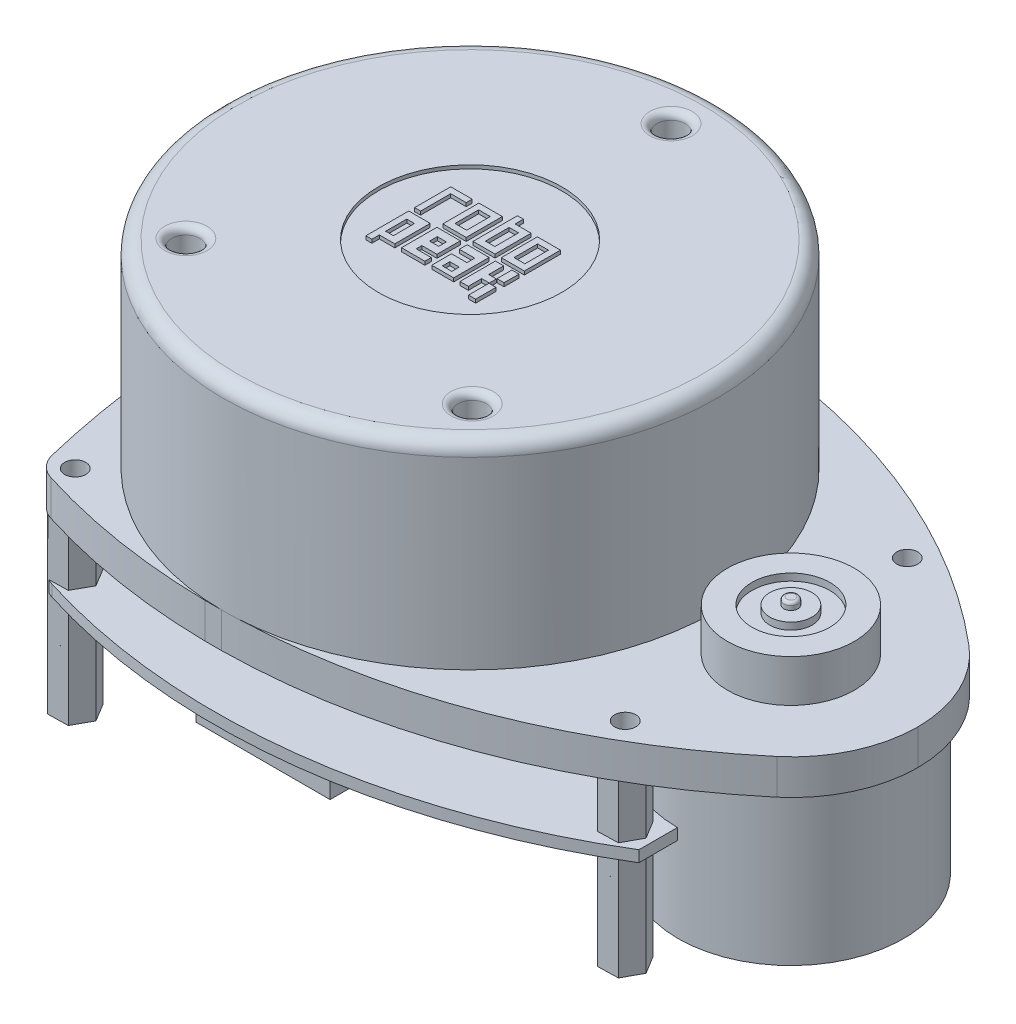
SolidWorks part; units mm, degrees
ref_plane "Спереди" through (0, 0, 0) normal (0, 0, 1) x (1, 0, 0)
ref_plane "Сверху" through (0, 0, 0) normal (0, 1, 0) x (1, 0, 0)
ref_plane "Справа" through (0, 0, 0) normal (1, 0, 0) x (0, 0, -1)
sketch "Эскиз1" plane through (0, 0, 0) normal (0, 1, 0) x (1, 0, 0)
  line L1 (-49.25, 35) -> (49.25, 35)
  line L2 (-49.25, 35) -> (-49.25, -35)
  line L3 (-49.25, -35) -> (49.25, -35)
  line L4 (49.25, 35) -> (49.25, -35)
  line L5 (-49.25, 35) -> (49.25, -35) construction
  line L6 (-49.25, -35) -> (49.25, 35) construction
  point P0 (0, 0)
  dimension "D1" = 98.5
  dimension "D2" = 70
extrude "Бобышка-Вытянуть1" add sketch "Эскиз1" along normal blind 5
sketch "Эскиз2" plane through (0, 5, 0) normal (0, 1, 0) x (1, 0, 0)
  line L0 (-49.25, 35) -> (-49.25, -35) construction
  circle A0 centre (-14.25, 0) radius 35
  point P2 (-49.25, 0)
  point P3 (-49.25, 0)
extrude "Бобышка-Вытянуть2" add sketch "Эскиз2" along normal blind 28.1
sketch "Эскиз3" plane through (0, 33.1, 0) normal (0, 1, 0) x (1, 0, 0)
  line L0 (-14.25, 0) -> (-14.25, 50000) construction
  line L1 (-14.25, -20) -> (-26.2883, -20) construction
  line L2 (-49.25, -35) -> (-14.25, -35) construction
  circle A0 centre (-14.25, 28.5) radius 2
  circle A1 centre (-34.5539, -20) radius 2
  circle A2 centre (6.0539, -20) radius 2
  arc A3 (-49.25, 0) -> (-14.25, -35) centre (-14.25, 0) ccw construction
  circle A4 centre (-14.25, 0) radius 35 construction
  dimension "D2" = 4
  dimension "D1" = 6.5
  dimension "D3" = 15
  dimension "D4" = 28.5
  dimension "D5" = 28.5
extrude "Вырез-Вытянуть1" cut sketch "Эскиз3" against normal blind 5
fillet "Скругление1" radius 2 1 edges at (-14.25, 33.1, 35)
fillet "Скругление2" radius 1 3 edges at (6.0539, 33.1, 22) (-34.5539, 33.1, 22) (-14.25, 33.1, -26.5)
sketch "Эскиз4" plane through (0, 33.1, 0) normal (0, 1, 0) x (1, 0, 0)
  line L0 (-22.1152, -6.9149) -> (-22.1152, -0.8316)
  line L1 (-22.1152, -0.8316) -> (-19.0735, -0.8316)
  line L2 (-19.0735, -0.8316) -> (-19.0735, -5.8538)
  line L3 (-19.0735, -5.8538) -> (-21.2663, -5.8538)
  line L4 (-21.2663, -5.8538) -> (-21.2663, -6.9149)
  line L5 (-21.2663, -6.9149) -> (-22.1152, -6.9149)
  line L6 (-22.1152, 0) -> (-22.1152, 5.1201)
  line L7 (-22.1152, 5.1201) -> (-19.0735, 5.1201)
  line L8 (-19.0735, 5.1201) -> (-19.0735, 4.2707)
  line L9 (-19.0735, 4.2707) -> (-21.2663, 4.2707)
  line L10 (-21.2663, 4.2707) -> (-21.2663, 0)
  line L11 (-21.2663, 0) -> (-22.1152, 0)
  line L12 (-21.2663, -1.9579) -> (-20.1699, -1.9579)
  line L13 (-20.1699, -1.9579) -> (-20.1699, -4.9509)
  line L14 (-20.1699, -4.9509) -> (-21.2663, -4.9509)
  line L15 (-21.2663, -4.9509) -> (-21.2663, -1.9579)
  line L16 (-13.8296, 0) -> (-13.8296, 6.293)
  line L17 (-18.1168, 0) -> (-14.8003, 0)
  line L18 (-18.1168, 0) -> (-18.1168, 5.1201)
  line L19 (-18.1168, 5.1201) -> (-14.8003, 5.1201)
  line L20 (-14.8003, 0) -> (-14.8003, 5.1201)
  line L21 (-9.8255, 5.1201) -> (-6.5494, 5.1201)
  line L22 (-9.8255, 5.1201) -> (-9.8255, 0)
  line L23 (-9.8255, 0) -> (-6.5494, 0)
  line L24 (-6.5494, 5.1201) -> (-6.5494, 0)
  line L25 (-8.9357, 4.2707) -> (-7.3988, 4.2707)
  line L26 (-8.9357, 4.2707) -> (-8.9357, 0.9137)
  line L27 (-8.9357, 0.9137) -> (-7.3988, 0.9137)
  line L28 (-7.3988, 4.2707) -> (-7.3988, 0.9137)
  line L29 (-17.3079, 4.2707) -> (-15.6497, 4.2707)
  line L30 (-17.3079, 4.2707) -> (-17.3079, 0.9137)
  line L31 (-17.3079, 0.9137) -> (-15.6497, 0.9137)
  line L32 (-15.6497, 4.2707) -> (-15.6497, 0.9137)
  line L33 (-12.9802, 4.2707) -> (-11.6455, 4.2707)
  line L34 (-12.9802, 4.2707) -> (-12.9802, 0.9137)
  line L35 (-12.9802, 0.9137) -> (-11.6455, 0.9137)
  line L36 (-11.6455, 4.2707) -> (-11.6455, 0.9137)
  line L37 (-12.9802, -4.142) -> (-11.6455, -4.142)
  line L38 (-12.9802, -4.142) -> (-12.9802, -5.1936)
  line L39 (-12.9802, -5.1936) -> (-11.6455, -5.1936)
  line L40 (-11.6455, -4.142) -> (-11.6455, -5.1936)
  line L41 (-16.9439, -1.9579) -> (-15.6497, -1.9579)
  line L42 (-16.9439, -1.9579) -> (-16.9439, -3.0499)
  line L43 (-16.9439, -3.0499) -> (-15.6497, -3.0499)
  line L44 (-15.6497, -1.9579) -> (-15.6497, -3.0499)
  line L46 (-7.5508, -0.7643) -> (-6.5494, -0.7643)
  line L47 (-7.5508, -0.7643) -> (-7.5508, -2.8858)
  line L48 (-7.5508, -2.8858) -> (-6.5494, -2.8858)
  line L49 (-6.5494, -0.7643) -> (-6.5494, -2.8858)
  line L50 (-6.5494, -6.9149) -> (-7.5508, -6.9149)
  line L51 (-6.5494, -6.9149) -> (-6.5494, -4.0216)
  line L52 (-6.5494, -4.0216) -> (-7.5508, -4.0216)
  line L53 (-13.8296, 6.293) -> (-12.9802, 6.293)
  line L54 (-12.9802, 6.293) -> (-12.9802, 5.1201)
  line L55 (-12.9802, 5.1201) -> (-10.7153, 5.1201)
  line L56 (-10.7153, 5.1201) -> (-10.7153, 0)
  line L57 (-10.7153, 0) -> (-13.8296, 0)
  line L58 (-9.8255, -0.8316) -> (-8.6437, -0.8316)
  line L59 (-8.6437, -0.8316) -> (-8.6437, -2.9608)
  line L60 (-8.6437, -2.9608) -> (-7.5508, -2.9608)
  line L61 (-9.8255, -0.8316) -> (-9.8255, -5.8538)
  line L62 (-9.8255, -5.8538) -> (-8.6437, -5.8538)
  line L63 (-8.6437, -5.8538) -> (-8.6437, -3.9573)
  line L64 (-8.6437, -3.9573) -> (-7.5508, -3.9573)
  line L65 (-7.5508, -2.9608) -> (-7.5508, -3.9573)
  line L66 (-13.8296, -0.8316) -> (-10.7153, -0.8316)
  line L67 (-10.7153, -0.8316) -> (-10.7153, -5.8538)
  line L68 (-10.7153, -5.8538) -> (-13.8296, -5.8538)
  line L69 (-13.8296, -5.8538) -> (-13.8296, -3.0499)
  line L70 (-13.8296, -3.0499) -> (-11.6455, -3.0499)
  line L71 (-11.6455, -3.0499) -> (-11.6455, -1.9408)
  line L72 (-11.6455, -1.9408) -> (-13.8296, -1.9408)
  line L73 (-13.8296, -1.9408) -> (-13.8296, -0.8316)
  line L74 (-18.1168, -0.8316) -> (-14.8003, -0.8316)
  line L75 (-14.8003, -0.8316) -> (-14.8003, -4.142)
  line L76 (-14.8003, -4.142) -> (-16.9439, -4.142)
  line L77 (-16.9439, -4.142) -> (-16.9439, -4.9509)
  line L78 (-16.9439, -4.9509) -> (-14.8003, -4.9509)
  line L79 (-14.8003, -4.9509) -> (-14.8003, -5.8538)
  line L80 (-14.8003, -5.8538) -> (-18.1168, -5.8538)
  line L81 (-18.1168, -5.8538) -> (-18.1168, -0.8316)
  line L82 (-7.5508, -6.9149) -> (-7.5508, -4.0216)
  circle A0 centre (-14.25, 0) radius 13
  dimension "D1" = 26
extrude "Вырез-Вытянуть3" cut sketch "Эскиз4" against normal blind 0.5 contours A0 L50 L82 L52 L51 L72 L73 L66 L67 L68 L69 L70 L71 L56 L57 L16 L53 L54 L55 L10 L11 L6 L7 L8 L9 L4 L5 L0 L1 L2 L3 L20 L17 L18 L19 L21 L24 L23 L22 L46 L49 L48 L47 | L32 L29 L30 L31 | L36 L33 L34 L35 | L28 L25 L26 L27 | L44 L41 L42 L43 | L15 L14 L13 L12 | L37 L40 L39 L38 region at (-20.7181, 33.1, 3.4544) region at (-8.1672, 33.1, -2.5922) region at (-16.4788, 33.1, -2.5922) region at (-12.3129, 33.1, -2.5922) region at (-16.2968, 33.1, 2.5039) region at (-14.2871, 33.1, -0.0991)
sketch "Эскиз5" plane through (0, 5, 0) normal (0, 1, 0) x (1, 0, 0)
  line L0 (-42.25, 30.7255) -> (-42.25, -39.5827) construction
  line L1 (27.75, 26.9972) -> (27.75, -49973.0028) construction
  line L2 (-49.25, 0) -> (49950.75, 0) construction
  circle A0 centre (-14.25, 0) radius 33 construction
  circle A1 centre (-42.25, 28) radius 1.25
  circle A2 centre (27.75, 20) radius 1.25
  circle A3 centre (27.75, -20) radius 1.25
  circle A4 centre (-42.25, -28) radius 1.25
  point P4 (-14.25, 33)
  dimension "D1" = 28
  dimension "D3" = 2.5
  dimension "D2" = 42
  dimension "D4" = 28
  dimension "D5" = 20
extrude "Вырез-Вытянуть4" cut sketch "Эскиз5" against normal blind 5
sketch "Эскиз6" plane through (0, 5, 0) normal (0, 1, 0) x (1, 0, 0)
  line L0 (49.25, 0) -> (50049.25, 0) construction
  line L1 (49.25, -35) -> (49.25, 35) construction
  circle A0 centre (31.25, 0) radius 9
  arc A1 (-14.25, -35) -> (-14.25, 35) centre (-14.25, 0) ccw construction
  point P4 (49.25, 0)
  dimension "D1" = 18
  dimension "D2" = 45.5
extrude "Бобышка-Вытянуть3" add sketch "Эскиз6" along normal blind 7
sketch "Эскиз7" plane through (0, 12, 0) normal (0, 1, 0) x (1, 0, 0)
  circle A0 centre (31.25, 0) radius 9
  circle A1 centre (31.25, 0) radius 0.9935
extrude "Вырез-Вытянуть5" cut sketch "Эскиз7" against normal blind 1
sketch "Эскиз8" plane through (0, 11, 0) normal (0, 1, 0) x (1, 0, 0)
  circle A0 centre (31.25, 0) radius 3.0011
  circle A1 centre (31.25, 0) radius 5.5217
extrude "Вырез-Вытянуть6" cut sketch "Эскиз8" against normal blind 1
fillet "Скругление3" radius 0.4 1 edges at (31.25, 12, 0.9935)
sketch "Эскиз9" plane through (0, 5, 0) normal (0, 1, 0) x (1, 0, 0)
  circle A0 centre (31.25, 0) radius 16
  dimension "D1" = 32
extrude "Бобышка-Вытянуть4" add sketch "Эскиз9" against normal blind 27
sketch "Эскиз10" plane through (0, 0, 0) normal (0, -1, 0) x (1, 0, 0)
  line L0 (-49.25, 0) -> (49950.75, 0) construction
  line L1 (-40.8546, 25.4729) -> (-39.3638, 27.9449)
  line L2 (-39.3638, 27.9449) -> (-40.7592, 30.472)
  line L3 (-40.7592, 30.472) -> (-43.6454, 30.5271)
  line L4 (-43.6454, 30.5271) -> (-45.1362, 28.0551)
  line L5 (-45.1362, 28.0551) -> (-43.7408, 25.528)
  line L6 (-43.7408, 25.528) -> (-40.8546, 25.4729)
  line L7 (29.2571, 22.4621) -> (26.3713, 22.5363)
  line L8 (26.3713, 22.5363) -> (24.8642, 20.0742)
  line L9 (24.8642, 20.0742) -> (26.2429, 17.5379)
  line L10 (26.2429, 17.5379) -> (29.1287, 17.4637)
  line L11 (29.1287, 17.4637) -> (30.6358, 19.9258)
  line L12 (30.6358, 19.9258) -> (29.2571, 22.4621)
  line L13 (30.6358, -19.9258) -> (29.2571, -22.4621)
  line L14 (29.1287, -17.4637) -> (30.6358, -19.9258)
  line L15 (26.2429, -17.5379) -> (29.1287, -17.4637)
  line L16 (24.8642, -20.0742) -> (26.2429, -17.5379)
  line L17 (26.3713, -22.5363) -> (24.8642, -20.0742)
  line L18 (29.2571, -22.4621) -> (26.3713, -22.5363)
  line L19 (-43.7408, -25.528) -> (-40.8546, -25.4729)
  line L20 (-45.1362, -28.0551) -> (-43.7408, -25.528)
  line L21 (-43.6454, -30.5271) -> (-45.1362, -28.0551)
  line L22 (-40.7592, -30.472) -> (-43.6454, -30.5271)
  line L23 (-39.3638, -27.9449) -> (-40.7592, -30.472)
  line L24 (-40.8546, -25.4729) -> (-39.3638, -27.9449)
  circle A0 centre (-42.25, 28) radius 2.5 construction
  circle A1 centre (27.75, 20) radius 2.5 construction
  circle A2 centre (27.75, -20) radius 2.5 construction
  circle A3 centre (-42.25, -28) radius 2.5 construction
  point P17 (27.75, 20)
  dimension "D1" = 5
  dimension "D2" = 5
extrude "Бобышка-Вытянуть5" add sketch "Эскиз10" along normal blind 24.6
sketch "Эскиз11" plane through (0, 5, 0) normal (0, 1, 0) x (1, 0, 0)
  circle A0 centre (-14.25, 0) radius 26
  dimension "D1" = 52
extrude "Бобышка-Вытянуть6" add sketch "Эскиз11" against normal blind 8
fillet "Скругление4" radius 1 1 edges at (-14.25, -3, 26)
sketch "Эскиз12" plane through (0, 5, 0) normal (0, 1, 0) x (1, 0, 0)
  line L1 (49.25, -35) -> (49.25, 35) construction
  line L2 (-49.25, 0) -> (-50049.25, 0) construction
  line L4 (-54.0511, 37.7308) -> (52.2004, 37.7308)
  line L5 (-54.0511, 37.7308) -> (-54.0511, -37.8351)
  line L6 (-54.0511, -37.8351) -> (52.2004, -37.8351)
  line L7 (52.2004, 37.7308) -> (52.2004, -37.8351)
  arc A0 (-49.25, 0) -> (-45.5286, 27.9743) centre (86.6751, -3.8473) cw
  circle A1 centre (-14.25, 0) radius 35 construction
  arc A3 (49.25, 0) -> (42.909, 13.5993) centre (31.4018, -0.0442) ccw
  arc A4 (-49.25, 0) -> (-14.25, -35) centre (-14.25, 0) ccw construction
  arc A5 (-42.835, 30.8555) -> (42.909, 13.5993) centre (-15.6796, -55.8665) cw
  arc A6 (-45.5286, 27.9743) -> (-42.835, 30.8555) centre (-41.6397, 27.0383) cw
  arc A7 (-45.5286, -27.9743) -> (-42.835, -30.8555) centre (-41.6397, -27.0383) ccw
  arc A8 (-42.835, -30.8555) -> (42.909, -13.5993) centre (-15.6796, 55.8665) ccw
  arc A9 (49.25, 0) -> (42.909, -13.5993) centre (31.4018, 0.0442) cw
  arc A10 (-49.25, 0) -> (-45.5286, -27.9743) centre (86.6751, 3.8473) ccw
  dimension "D1" = 4
extrude "Вырез-Вытянуть7" cut sketch "Эскиз12" against normal blind 8
fillet "Скругление5" radius 100 1 edges at (-49.25, 2.5, 0)
sketch "Эскиз13" plane through (0, 0, 0) normal (0, -1, 0) x (1, 0, 0)
  line L0 (31.5536, 21.8603) -> (31.5536, 16.4)
  line L1 (31.5536, -16.4) -> (31.5536, -21.8603)
  arc A0 (-49.0982, 0) -> (-45.3768, 27.9743) centre (86.8269, -3.8473) cw
  arc A1 (31.5536, 16.4) -> (31.5536, -16.4) centre (31.5536, 0) ccw
  arc A2 (-42.6831, 30.8555) -> (31.5536, 21.8603) centre (-15.5278, -55.8665) cw
  arc A3 (-45.3768, 27.9743) -> (-42.6831, 30.8555) centre (-41.4878, 27.0383) cw
  arc A4 (-45.3768, -27.9743) -> (-42.6831, -30.8555) centre (-41.4878, -27.0383) ccw
  arc A5 (-42.6831, -30.8555) -> (31.5536, -21.8603) centre (-15.5278, 55.8665) ccw
  arc A7 (-49.0982, 0) -> (-45.3768, -27.9743) centre (86.8269, 3.8473) ccw
  arc A8 (-48.5248, 10.6929) -> (-48.5248, -10.6929) centre (50.9018, 0) ccw construction
  point P16 (-49.0982, 0)
  point P21 (-49.0982, 0)
  dimension "D1" = 4
  dimension "D2" = 32.8
extrude "Бобышка-Вытянуть7" add sketch "Эскиз13" along normal blind 1.6 from offset 8
sketch "Эскиз14" plane through (0, -9.6, 0) normal (0, -1, 0) x (1, 0, 0)
  line L1 (-24.0982, 30) -> (-4.0982, 30)
  line L2 (-24.0982, 30) -> (-24.0982, 25)
  line L3 (-24.0982, 25) -> (-4.0982, 25)
  line L4 (-4.0982, 30) -> (-4.0982, 25)
  circle A0 centre (-14.25, 0) radius 35 construction
  point P4 (-14.0982, 30)
  dimension "D1" = 5
  dimension "D2" = 20
  dimension "D3" = 35
  dimension "D4" = 30
extrude "Бобышка-Вытянуть8" add sketch "Эскиз14" along normal blind 6
chamfer "Фаска1" distance 1 angle 45 1 edges at (-24.0982, -12.6, 30)
ref_plane "Plane1" through (0, -25, 0) normal (0, 1, 0) x (1, 0, 0)
sketch "Sketch1" plane through (0, -25, 0) normal (0, 1, 0) x (1, 0, 0)
  line L0 (-40.8546, -25.4729) -> (-43.6454, -30.5271) construction
  line L1 (-43.7408, 25.528) -> (-40.7592, 30.472) construction
  line L2 (24.8642, 20.0742) -> (30.6358, 19.9258) construction
  line L3 (24.8642, -20.0742) -> (30.6358, -19.9258) construction
  circle A0 centre (-42.25, -28) radius 1.5
  circle A1 centre (-42.25, 28) radius 1.5
  circle A2 centre (27.75, 20) radius 1.5
  circle A3 centre (27.75, -20) radius 1.5
  dimension "D1" = 3
  dimension "D2" = 3
  dimension "D3" = 3
  dimension "D4" = 3
extrude "Cut-Extrude1" cut sketch "Sketch1" along normal blind 30
sketch "Sketch3" plane through (0, 33.1, 0) normal (0, 1, 0) x (1, 0, 0)
